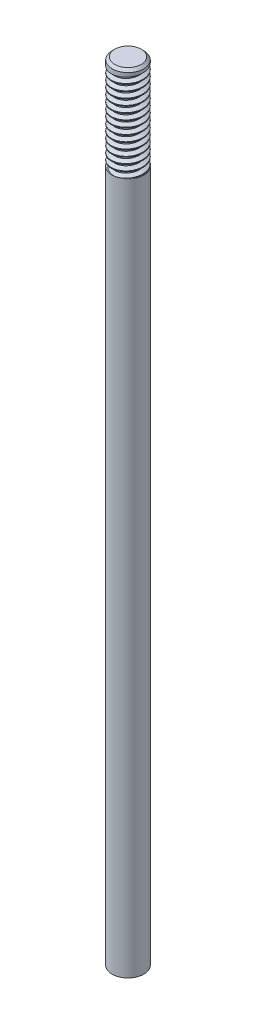
SolidWorks part; units mm, degrees
material "Alloy Steel (SS)"
ref_plane "Front Plane" through (0, 0, 0) normal (0, 0, 1) x (1, 0, 0)
ref_plane "Top Plane" through (0, 0, 0) normal (0, 1, 0) x (1, 0, 0)
ref_plane "Right Plane" through (0, 0, 0) normal (1, 0, 0) x (0, 0, -1)
sketch "Sketch1" plane through (0, 0, 0) normal (0, 1, 0) x (1, 0, 0)
  circle A0 centre (0, 0) radius 1.5939
  dimension "D1" = 3.1877
extrude "Boss-Extrude1" add sketch "Sketch1" along normal blind 79.248
sketch "Sketch2" plane through (0, 79.248, 0) normal (0, 1, 0) x (1, 0, 0)
  circle A0 centre (0, 0) radius 1.5875
  dimension "D1" = 3.175
extrude "Cut-Extrude1" cut sketch "Sketch2" against normal blind 9.525 flip side to cut
cosmetic thread "Cosmetic Thread1" parameters "D2"=2.4181
chamfer "Chamfer1" distance 0.254 angle 45 1 edges at (0, 79.248, 1.5875)
thread "Thread5" pitch 0.635 method cut trim with start face yes trim with end face yes profile "Thread Profile1" start angle 0, offset 0, length 0, pitch 0.635, diameter 3.175
ref_plane "Plane1" through (-1.5875, 78.994, 0) normal (0, 0, 1) x (-1, 0, 0)
sketch "Thread Profile1" plane through (-1.5875, 78.994, 0) normal (0, 0, 1) x (-1, 0, 0)
  line L0 (0, 0) -> (0, 0.635) construction
  line L11 (0, 0) -> (0, 0.5556)
  line L12 (0, 0.5556) -> (-0.3437, 0.3572)
  line L13 (-0.3437, 0.3572) -> (-0.3437, 0.1984)
  line L15 (-0.3437, 0.1984) -> (0, 0)
  line L17 (-0.3437, 0.2778) -> (0, 0.2778) construction
  point P2 (0, 0)
  dimension "Pitch" = 0.635
  dimension "Profile_Angle" = 60
  dimension "Profile_Land" = 0.1588
  dimension "Profile_Height" = 0.3437
